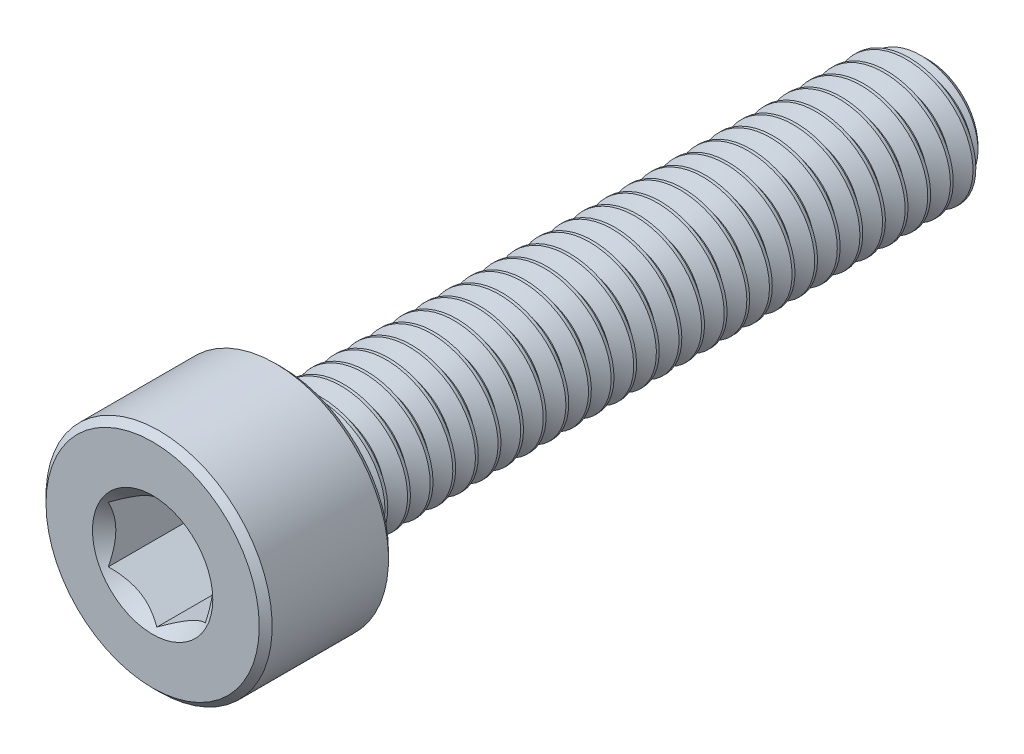
SolidWorks part; units mm, degrees
ref_plane "Front Plane" through (0, 0, 0) normal (0, 0, 1) x (1, 0, 0)
ref_plane "Top Plane" through (0, 0, 0) normal (0, 1, 0) x (1, 0, 0)
ref_plane "Right Plane" through (0, 0, 0) normal (1, 0, 0) x (0, 0, -1)
sketch "Sketch1" plane through (0, 0, 0) normal (1, 0, 0) x (0, 0, -1)
  line L0 (-12, 0) -> (12, 0) construction
  line L1 (12, 0) -> (12, 1.5453) construction
  line L2 (12, 1.5453) -> (11.5453, 2) construction
  line L3 (11.5453, 2) -> (11.475, 2) construction
  line L4 (11.475, 2) -> (-8, 2) construction
  line L5 (-8, 2) -> (-8, 3.5) construction
  line L6 (-8, 3.5) -> (-12, 3.5) construction
  line L7 (-12, 3.5) -> (-12, 0) construction
  line L8 (12, 1.5453) -> (12, 2) construction
  line L9 (11.9562, 2.0758) -> (12.3062, 1.4696) construction
  line L10 (12.3062, 1.4696) -> (12.6562, 2.0758) construction
  line L11 (12.6562, 2.0758) -> (11.9562, 2.0758) construction
  line L12 (12.3062, 2.0758) -> (12.3063, 2) construction
  line L13 (12.3062, 1.4696) -> (12.3063, 1.5453) construction
  line L14 (12.2625, 1.5453) -> (12.35, 1.5453) construction
  line L15 (12, 2) -> (12.6125, 2) construction
  line L16 (11.9781, 2.0379) -> (12.6344, 2.0379) construction
  line L17 (12, 0) -> (12, -2) construction
  line L18 (-8.2, 3.5) -> (-8, 3.3) construction
  line L19 (-11.8, 3.5) -> (-12, 3.3) construction
  line L20 (-8, 2) -> (-8, 0) construction
  line L21 (-8, 1) -> (-1.3333, 1) construction
  line L22 (-1.3333, 1) -> (5.3333, 1) construction
  line L23 (5.3333, 1) -> (12, 1) construction
  line L24 (-1.3333, 1) -> (-1.3333, 2) construction
  line L25 (-1.3333, 2) -> (-1.3333, 3.5) construction
  line L26 (5.3333, 1) -> (5.3333, 3.5) construction
  point P0 (-12, 1.5)
  point P3 (10.25, 2)
  point P4 (0, 0)
  point P18 (5.3333, 2)
  point P22 (12.3063, 1.5453)
  point P24 (11.475, 2)
  point P25 (12.3063, 2)
  point P28 (12.3063, 2.0379)
  point P29 (10.25, -2)
  point P30 (-1.3333, 2)
  point P31 (-10, 3.5)
  point P37 (-8.7, 3.5)
  point P38 (-11.7, 3.5)
  point P45 (-1.3333, 1)
  point P46 (5.3333, 1)
  dimension "D2" = 0.0875
  dimension "D7" = 0.2
  dimension "D8" = 0.2
  dimension "D9" = 0.2
  dimension "D10" = 0.1
  dimension "D11" = 0.5
  dimension "Drive Size" = 3
  dimension "Head Diameter" = 7
  dimension "Head Height" = 4
  dimension "Thread Pitch" = 0.7
  dimension "Thread Size" = 4
  dimension "Length" = 20
  dimension "D12" = 0.525
  dimension "D4" = 1.75
  dimension "D3" = 45
sketch "Sketch2" plane through (0, 0, 0) normal (1, 0, 0) x (0, 0, -1)
  line L0 (-12, 0) -> (-12, 3.3)
  line L1 (-11.8, 3.5) -> (-8.2, 3.5)
  line L2 (-8, 3.3) -> (-8, 2.2)
  line L4 (11.5453, 2) -> (12, 1.5453)
  line L5 (12, 1.5453) -> (12, 0)
  line L6 (-8, 3.5) -> (-12, 3.5) construction
  line L7 (12, 0) -> (-12, 0)
  line L8 (-11.8, 3.5) -> (-12, 3.3) construction
  line L10 (-11.8, 3.5) -> (-12, 3.3)
  line L14 (-8.2, 3.5) -> (-8, 3.3) construction
  line L16 (-8.2, 3.5) -> (-8, 3.3)
  line L17 (-8, 2) -> (-8, 3.5) construction
  line L19 (-7.8, 2) -> (11.5453, 2)
  line L20 (11.475, 2) -> (-8, 2) construction
  arc A1 (-8, 2.2) -> (-7.8, 2) centre (-7.8, 2.2) ccw
  dimension "D3" = 0.2
revolve "Revolve1" add sketch "Sketch2" angle 360 about L7
sketch "Sketch3" plane through (0, 0, 12) normal (0, 0, 1) x (1, 0, 0)
  line L1 (1.5, -0.866) -> (1.5, 0.866)
  line L2 (1.5, 0.866) -> (0, 1.7321)
  line L3 (0, 1.7321) -> (-1.5, 0.866)
  line L4 (-1.5, 0.866) -> (-1.5, -0.866)
  line L5 (-1.5, -0.866) -> (0, -1.7321)
  line L6 (0, -1.7321) -> (1.5, -0.866)
  circle A0 centre (0, 0) radius 1.5 construction
  circle A1 centre (0, 0) radius 3.5 construction
  circle A2 centre (0, 0) radius 3.5 construction
  circle A3 centre (0, 0) radius 1.7321 construction
  point P13 (0, 0)
  dimension "D1" = 3.4641
extrude "Cut-Extrude1" cut sketch "Sketch3" against normal offset from surface (3 mm away) 1 up to face at (0, 3.3, 8)
sketch "Sketch4" plane through (0, 0, 12) normal (0, 0, 1) x (1, 0, 0)
  circle A0 centre (0, 0) radius 1.862
  dimension "D1" = 3.7239
extrude "Cut-Extrude2" cut sketch "Sketch4" against normal up to vertex (2 mm away) draft 45 up to point (0, 3.5, 10)
sketch "Sketch11" plane through (0, 0, 0) normal (1, 0, 0) x (0, 0, -1)
  line L0 (-12, 0) -> (12, 0) construction
  line L1 (-12, 0) -> (12, 0) construction
  line L2 (-4.25, 0) -> (-4.25, 2) construction
  line L3 (11.475, 2) -> (-8, 2) construction
  line L4 (8.25, 0) -> (8.25, 2) construction
  line L6 (12, 1.5453) -> (12, 2) construction
  point P2 (-4.25, 0)
  point P3 (8.25, 0)
  dimension "D1" = 3.75
  dimension "D2" = 3.75
sketch "Sketch6" plane through (0, 0, -12) normal (0, 0, -1) x (-1, 0, 0)
  circle A0 centre (0, 0) radius 2
curve "Helix/Spiral1" pitch 0.7 height 20.7 turns 29.5714
sketch "Sketch10" plane through (0, 0, 0) normal (1, 0, 0) x (0, 0, -1)
  line L0 (-7.8, -3.5) -> (-7.8, 3.5)
  line L5 (-12, 0) -> (12, 0) construction
  line L6 (-7.8, 2) -> (-7.8, -2) construction
  point P3 (-7.8, 0)
split "Split1" trim tools "Sketch10" bodies to split 106 resulting bodies 114 115
sketch "Sketch7" plane through (0, 0, 0) normal (1, 0, 0) x (0, 0, -1)
  line L0 (11.9781, 2.0379) -> (12.6344, 2.0379)
  line L1 (12.6344, 2.0379) -> (12.35, 1.5453)
  line L2 (12.35, 1.5453) -> (12.2625, 1.5453)
  line L3 (12.2625, 1.5453) -> (11.9781, 2.0379)
sweep "Cut-Sweep1" cut profiles "Sketch7" path "Helix/Spiral1"
sketch "Sketch8" plane through (0, 0, 0) normal (1, 0, 0) x (0, 0, -1)
  line L0 (-8, 0) -> (-8, 2)
  line L1 (-7.8, -2) -> (-7.8, 2) construction
  line L2 (-8, 2) -> (-7.8, 2)
  line L4 (-7.8, 2) -> (-6.6453, 0)
  line L5 (-6.6453, 0) -> (-8, 0)
  line L6 (11.475, 2) -> (-8, 2) construction
  line L7 (-12, 0) -> (12, 0) construction
  dimension "D1" = 60
revolve "Revolve2" add sketch "Sketch8" angle 360 about L5
equation "\"D2@Sketch1\" = \"Thread Pitch@Sketch1\" / 8"
equation "\"D4@Helix/Spiral1\" = \"Thread Pitch@Sketch1\""
equation "\"D7@Sketch1\" = \"Head Height@Sketch1\" * .05"
equation "\"D8@Sketch1\"=\"D7@Sketch1\""
equation "\"D9@Sketch1\"=\"D7@Sketch1\""
equation "\"D10@Sketch1\"=\"D7@Sketch1\"/2"
equation "\"D11@Sketch1\"=\"D10@Sketch1\"*5"
equation "\"D4@Sketch1\"=\"Thread Pitch@Sketch1\"*2.5"
equation "\"D12@Sketch1\"=\"Thread Pitch@Sketch1\"*.75"
equation "\"D3@Helix/Spiral1\"=\"Length@Sketch1\"+\"Thread Pitch@Sketch1\""
equation "\"D3@Sketch2\"=\"Thread Size@Sketch1\"*0.05"
equation "\"D1@Sketch11\"=\"Length@Sketch1\"*0.1875"
equation "\"D2@Sketch11\"=\"D1@Sketch11\""
equation "\"D1@Sketch4\"=\"D1@Sketch3\"*1.075"
